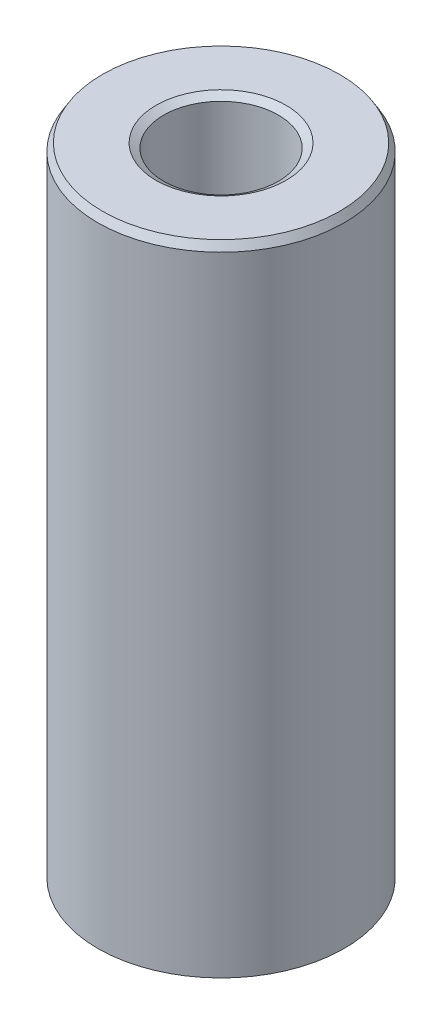
SolidWorks part; units mm, degrees
ref_plane "Front Plane" through (0, 0, 0) normal (0, 0, 1) x (1, 0, 0)
ref_plane "Top Plane" through (0, 0, 0) normal (0, 1, 0) x (1, 0, 0)
ref_plane "Right Plane" through (0, 0, 0) normal (1, 0, 0) x (0, 0, -1)
sketch "Sketch1" plane through (0, 0, 0) normal (0, 1, 0) x (1, 0, 0)
  circle A0 centre (0, 0) radius 7.5
  dimension "SLEEVE_OD" = 15
extrude "Boss-Extrude1" add sketch "Sketch1" along normal blind 39.0098
sketch "Sketch2" plane through (0, 0, 0) normal (0, 1, 0) x (1, 0, 0)
  circle A0 centre (0, 0) radius 3.4939
  dimension "BORE_D" = 6.9877
extrude "Cut-Extrude1" cut sketch "Sketch2" along normal through all
chamfer "Chamfer1" distance 0.4669 angle 31.025 4 edges at (0, 39.0098, 3.4939) (0, 0, 3.4939) (0, 0, 7.5) (0, 39.0098, 7.5) first distance on face at (0, 39.0098, 3.4939) first distance on face at (0, 0, 3.4939) first distance on face at (0, 39.0098, 7.5)
